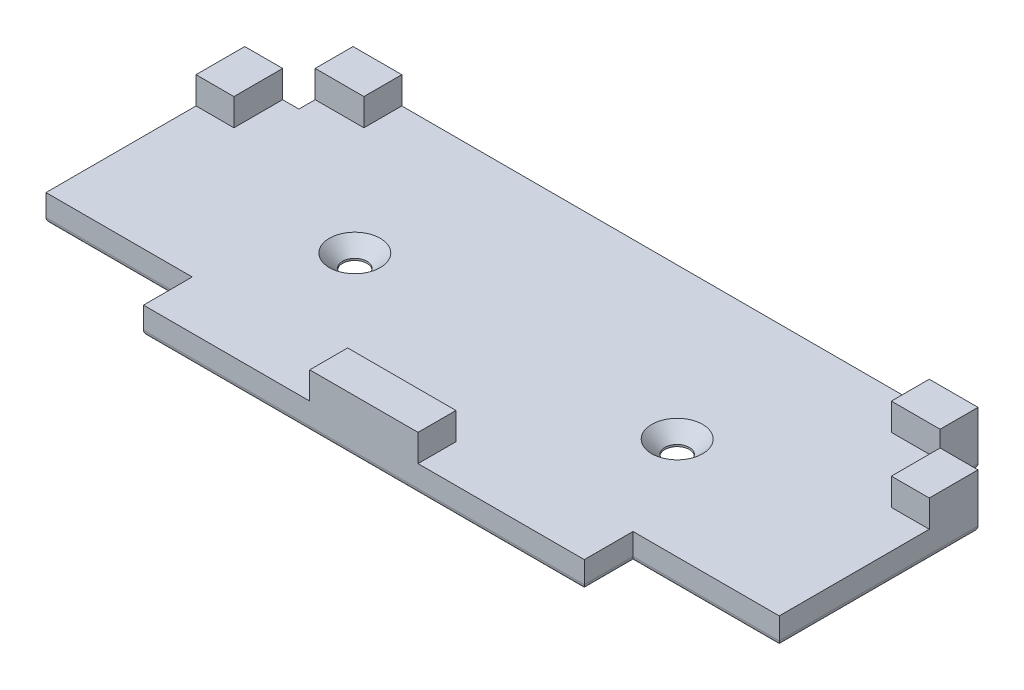
SolidWorks part; units mm, degrees
ref_plane "Front Plane" through (0, 0, 0) normal (0, 0, 1) x (1, 0, 0)
ref_plane "Top Plane" through (0, 0, 0) normal (0, 1, 0) x (1, 0, 0)
ref_plane "Right Plane" through (0, 0, 0) normal (1, 0, 0) x (0, 0, -1)
sketch "Sketch1" plane through (0, 0, 0) normal (0, 1, 0) x (1, 0, 0)
  line L0 (67.7, 27.85) -> (-67.7, 27.85)
  line L1 (60.7, -20.85) -> (-60.7, -20.85) construction
  line L2 (60.7, -20.85) -> (60.7, 20.85) construction
  line L3 (60.7, 20.85) -> (-60.7, 20.85) construction
  line L4 (-60.7, -20.85) -> (-60.7, 20.85) construction
  line L5 (60.7, -20.85) -> (-60.7, 20.85) construction
  line L6 (60.7, 20.85) -> (-60.7, -20.85) construction
  line L7 (-67.7, -27.85) -> (-67.7, 27.85)
  line L8 (67.7, -27.85) -> (-67.7, -27.85)
  line L9 (67.7, -27.85) -> (67.7, 27.85)
  point P0 (0, 0)
  dimension "D1" = 41.7
  dimension "D2" = 121.4
  dimension "D3" = 7
extrude "Boss-Extrude1" add sketch "Sketch1" along normal blind 5
sketch "Sketch2" plane through (0, 5, 0) normal (0, 1, 0) x (1, 0, 0)
  line L1 (60.7, 20.85) -> (-60.7, 20.85) construction
  line L3 (-60.7, -20.85) -> (-60.7, 20.85) construction
  line L5 (-48.7, 20.85) -> (-60.7, 20.85)
  line L7 (-60.7, 8.85) -> (-60.7, 20.85)
  line L8 (-48.7, 20.85) -> (-48.7, 27.85)
  line L9 (67.7, 27.85) -> (-67.7, 27.85) construction
  line L10 (-48.7, 27.85) -> (-67.7, 27.85)
  line L11 (-67.7, 27.85) -> (-67.7, 8.85)
  line L12 (-67.7, -27.85) -> (-67.7, 27.85) construction
  line L13 (-67.7, 8.85) -> (-60.7, 8.85)
  line L14 (-60.7, 8.85) -> (-60.7, 20.85)
  line L15 (60.7, -20.85) -> (-60.7, -20.85) construction
  line L16 (-10, -27.85) -> (10, -27.85)
  line L17 (-10, -27.85) -> (-10, -20.85)
  line L18 (-10, -20.85) -> (10, -20.85)
  line L19 (10, -27.85) -> (10, -20.85)
  line L20 (-10, -27.85) -> (10, -20.85) construction
  line L21 (-10, -20.85) -> (10, -27.85) construction
  line L22 (67.7, -27.85) -> (-67.7, -27.85) construction
  line L23 (0, 0) -> (0, -24.35) construction
  line L24 (60.7, 8.85) -> (60.7, 20.85)
  line L25 (67.7, 8.85) -> (60.7, 8.85)
  line L26 (67.7, 27.85) -> (67.7, 8.85)
  line L27 (48.7, 27.85) -> (67.7, 27.85)
  line L28 (48.7, 20.85) -> (48.7, 27.85)
  line L29 (60.7, 8.85) -> (60.7, 20.85)
  line L30 (48.7, 20.85) -> (60.7, 20.85)
  point P0 (0, -24.35)
  line M8 (67.7, -27.85) -> (67.7, 27.85)
  line M9 (67.7, 27.85) -> (-67.7, 27.85)
  line M10 (-67.7, 27.85) -> (-67.7, -27.85)
  line M11 (-67.7, -27.85) -> (67.7, -27.85)
  dimension "D1" = 12
  dimension "D2" = 20
extrude "Boss-Extrude2" add sketch "Sketch2" along normal blind 5 contours L13 L7 L5 L8 M10 M9 | L19 L18 L17 M11 | L28 L30 L24 L25 M8 M9 region at (-54.7, 5, -21.1187) region at (58.2, 5, -27.5813) region at (0, 5, 24.35)
sketch "Sketch3" plane through (0, 5, 0) normal (0, 1, 0) x (1, 0, 0)
  line L0 (-60.7, -20.85) -> (-60.7, 20.85) construction
  line L1 (-67.7, -27.85) -> (-40.7, -27.85)
  line L2 (-67.7, -27.85) -> (-67.7, -18.85)
  line L3 (-67.7, -18.85) -> (-40.7, -18.85)
  line L4 (-40.7, -27.85) -> (-40.7, -18.85)
  dimension "D1" = 9
  dimension "D2" = 20
extrude "Cut-Extrude1" cut sketch "Sketch3" against normal through all
mirror "Mirror1" about plane through (0, 0, 0) normal (1, 0, 0) of "Cut-Extrude1"
sketch "Sketch4" plane through (0, 5, 0) normal (0, -1, 0) x (1, 0, 0)
  line L0 (0, 0) -> (-30, 0) construction
  line L1 (-30, 0) -> (0, 0) construction
  line L2 (0, 0) -> (30, 0) construction
  point P5 (-30, 0)
  point P6 (30, 0)
  dimension "D1" = 30
hole_wizard "CSK for M4 Countersunk Flat Head1" positions "3DSketch2" profile "Sketch6" countersink size "M4" standard "BSI" end condition through all
sketch3d "3DSketch2"
  line L0 (0, 5, 0) -> (-30, 5, 0) construction
  point P0 (-29.5278, 5, 0)
  point P4 (30, 5, 0)
sketch "Sketch6" plane through (-29.5278, 5, 0) normal (1, 0, 0) x (0, 0, 1)
  line L0 (0, 0) -> (0, 5)
  line L1 (0, 5) -> (2.25, 5)
  line L2 (2.25, 5) -> (2.25, 2.45)
  line L3 (2.25, 2.45) -> (4.7, 0)
  line L5 (4.7, 0) -> (0, 0)
  line L6 (-2.25, 2.45) -> (-4.7, 0) construction
  line L11 (0, -6.35) -> (0, 107.95) construction
  dimension "Thru Hole Dia." = 4.5
  dimension "Thru Hole Depth" = 5
  dimension "Near C'Sink Dia." = 9.4
  dimension "Near C'Sink Angle" = 90
sketch "Sketch7" plane through (0, 0, 0) normal (0, -1, 0) x (1, 0, 0)
  line L1 (-45, -15) -> (-15, -15)
  line L2 (-45, -15) -> (-45, 15)
  line L3 (-45, 15) -> (-15, 15)
  line L4 (-15, -15) -> (-15, 15)
  line L5 (-45, -15) -> (-15, 15) construction
  line L6 (-45, 15) -> (-15, -15) construction
  line L7 (15, -15) -> (45, -15)
  line L8 (15, -15) -> (15, 15)
  line L9 (15, 15) -> (45, 15)
  line L10 (45, -15) -> (45, 15)
  line L11 (15, -15) -> (45, 15) construction
  line L12 (15, 15) -> (45, -15) construction
  point P0 (-30, 0)
  point P6 (30, 0)
  dimension "D1" = 30
extrude "Cut-Extrude2" cut sketch "Sketch7" against normal blind 2.2
sketch "Sketch8" plane through (67.7, 0, 0) normal (1, 0, 0) x (0, 0, -1)
  line L0 (0, 0) -> (22, 0) construction
  line L1 (-18.85, 0) -> (27.85, 0) construction
  line L2 (0, 0) -> (22, 0) construction
  line L3 (-27.85, 0) -> (-18.85, 0) construction
  line L4 (0, 0) -> (0, 5) construction
  line L5 (19.5, -10) -> (24.5, -10)
  line L6 (19.5, -10) -> (19.5, 10)
  line L7 (19.5, 10) -> (24.5, 10)
  line L8 (24.5, -10) -> (24.5, 10)
  line L9 (19.5, -10) -> (24.5, 10) construction
  line L10 (19.5, 10) -> (24.5, -10) construction
  line L11 (-18.85, 5) -> (8.85, 5) construction
  dimension "D1" = 22
  dimension "D2" = 10
  dimension "D3" = 5
sketch "Sketch9" plane through (0, 10, 0) normal (0, 1, 0) x (1, 0, 0)
  line L1 (67.7, 27.85) -> (57.7, 27.85)
  line L2 (67.7, 27.85) -> (67.7, 17.85)
  line L3 (67.7, 17.85) -> (57.7, 17.85)
  line L4 (57.7, 27.85) -> (57.7, 17.85)
  dimension "D1" = 10
  dimension "D2" = 10
extrude "Cut-Extrude5" cut sketch "Sketch9" against normal through all
mirror "Mirror2" about plane through (0, 0, 0) normal (1, 0, 0) of "Cut-Extrude5"
fillet "Fillet1" radius 1 12 edges at (-57.7, 0, -22.85) (-62.7, 0, -17.85) (-67.7, 0, 0.5) (-54.2, 0, 18.85) (-40.7, 0, 23.35) (40.7, 0, 23.35) (0, 0, 27.85) (0, 0, -27.85) (57.7, 0, -22.85) (62.7, 0, -17.85) (54.2, 0, 18.85) (67.7, 0, 0.5)
